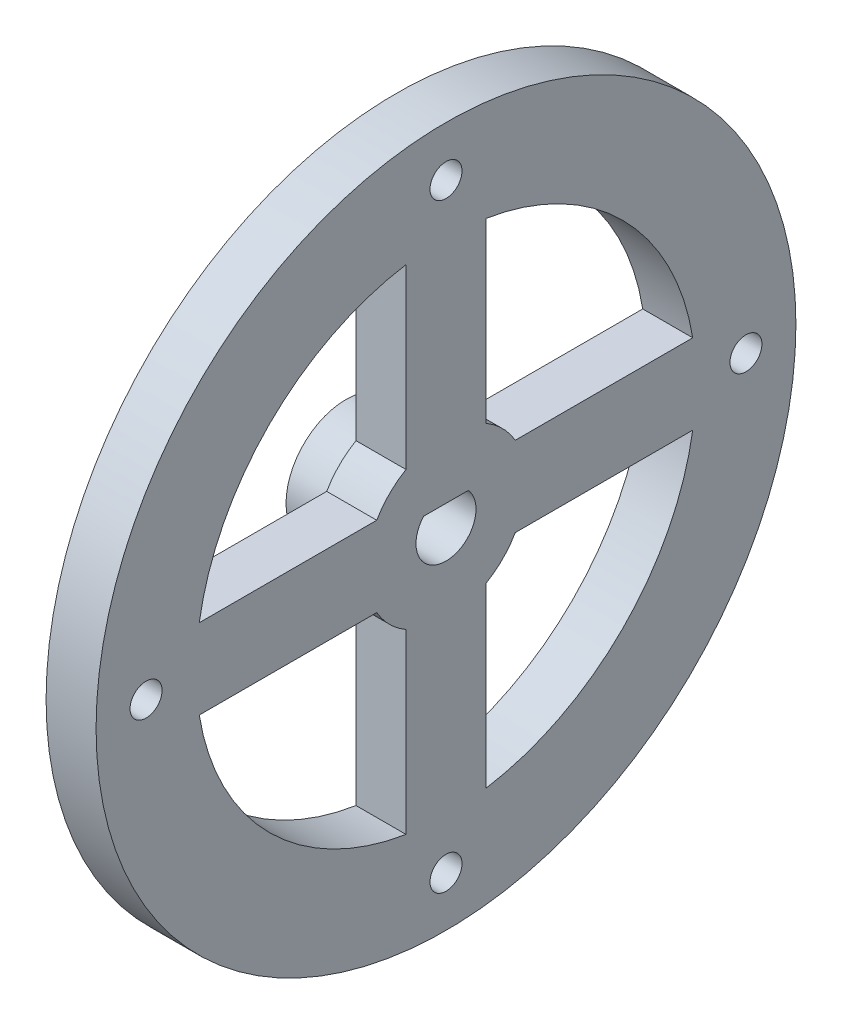
SolidWorks part; units mm, degrees
ref_plane "Front Plane" through (0, 0, 0) normal (0, 0, 1) x (1, 0, 0)
ref_plane "Top Plane" through (0, 0, 0) normal (0, 1, 0) x (1, 0, 0)
ref_plane "Right Plane" through (0, 0, 0) normal (1, 0, 0) x (0, 0, -1)
sketch "Sketch1" plane through (0, 0, 0) normal (1, 0, 0) x (0, 0, -1)
  line L0 (0, 0) -> (0, 50000) construction
  line L1 (4, 6.9282) -> (4, 24.6779)
  line L2 (-4, 24.6779) -> (-4, 6.9282)
  line L3 (-24.6779, -4) -> (-6.9282, -4)
  line L4 (-6.9282, 4) -> (-24.6779, 4)
  line L5 (4, -24.6779) -> (4, -6.9282)
  line L6 (-4, -6.9282) -> (-4, -24.6779)
  line L7 (24.6779, 4) -> (6.9282, 4)
  line L8 (6.9282, -4) -> (24.6779, -4)
  line L9 (2.2361, 2) -> (-2.2361, 2)
  circle A0 centre (0, 0) radius 35
  arc A1 (-2.2361, 2) -> (2.2361, 2) centre (0, 0) ccw
  arc A2 (-6.9282, -4) -> (-4, -6.9282) centre (0, 0) ccw
  arc A3 (-24.6779, -4) -> (-4, -24.6779) centre (0, 0) ccw
  arc A4 (-4, 6.9282) -> (-6.9282, 4) centre (0, 0) ccw
  arc A5 (24.6779, 4) -> (4, 24.6779) centre (0, 0) ccw
  arc A6 (4, -24.6779) -> (24.6779, -4) centre (0, 0) ccw
  arc A7 (4, -6.9282) -> (6.9282, -4) centre (0, 0) ccw
  arc A8 (6.9282, 4) -> (4, 6.9282) centre (0, 0) ccw
  arc A9 (-24.6779, 4) -> (-4, 24.6779) centre (0, 0) cw
  point P27 (0, 0)
  dimension "D1" = 70
  dimension "D2" = 6
  dimension "D5" = 16
  dimension "D6" = 50
  dimension "D3" = 8
  dimension "D7" = 2
  dimension "D4" = 4
extrude "Boss-Extrude1" add sketch "Sketch1" along normal blind 5
sketch "Sketch2" plane through (0, 0, 0) normal (-1, 0, 0) x (0, 0, 1)
  circle A0 centre (0, 0) radius 30 construction
  circle A1 centre (0, 30) radius 1.6
  circle A2 centre (30, 0) radius 1.6
  circle A3 centre (0, -30) radius 1.6
  circle A4 centre (-30, 0) radius 1.6
  point P14 (0, 0)
  dimension "D1" = 60
  dimension "D2" = 3.2
  dimension "D3" = 4
extrude "Cut-Extrude1" cut sketch "Sketch2" against normal through all
sketch "Sketch3" plane through (0, 0, 0) normal (-1, 0, 0) x (0, 0, 1)
  line L0 (-2.2361, 2) -> (2.2361, 2) construction
  line L1 (-2.2361, 2) -> (2.2361, 2)
  circle A2 centre (0, 0) radius 6
  arc A3 (-2.2361, 2) -> (2.2361, 2) centre (0, 0) ccw construction
  arc A4 (-2.2361, 2) -> (2.2361, 2) centre (0, 0) ccw
  dimension "D1" = 12
extrude "Boss-Extrude2" add sketch "Sketch3" along normal blind 5
sketch "Sketch6" plane through (0, 0, 0) normal (-1, 0, 0) x (0, 0, 1)
  circle A0 centre (0, 30) radius 3
  circle A1 centre (30, 0) radius 3
  circle A2 centre (0, -30) radius 3
  circle A3 centre (-30, 0) radius 3
  point P12 (0, 0)
  dimension "D1" = 6
  dimension "D2" = 4
extrude "Cut-Extrude2" cut sketch "Sketch6" against normal blind 2
sketch "Sketch7" plane through (-5, 0, 0) normal (-1, 0, 0) x (0, 0, 1)
  line L0 (-3.9116, -3.3007) -> (-3.9116, 3.3007)
  line L1 (3.9116, 3.3007) -> (3.9116, -3.3007)
  arc A2 (-3.9116, -3.3007) -> (3.9116, -3.3007) centre (0, 0) ccw
  arc A3 (3.9116, 3.3007) -> (-3.9116, 3.3007) centre (0, 0) ccw
  dimension "D2" = 10.2362
  dimension "D1" = 7.8232
extrude "Cut-Extrude3" cut sketch "Sketch7" against normal blind 2.3876 contours A3 L0 A2 L1
